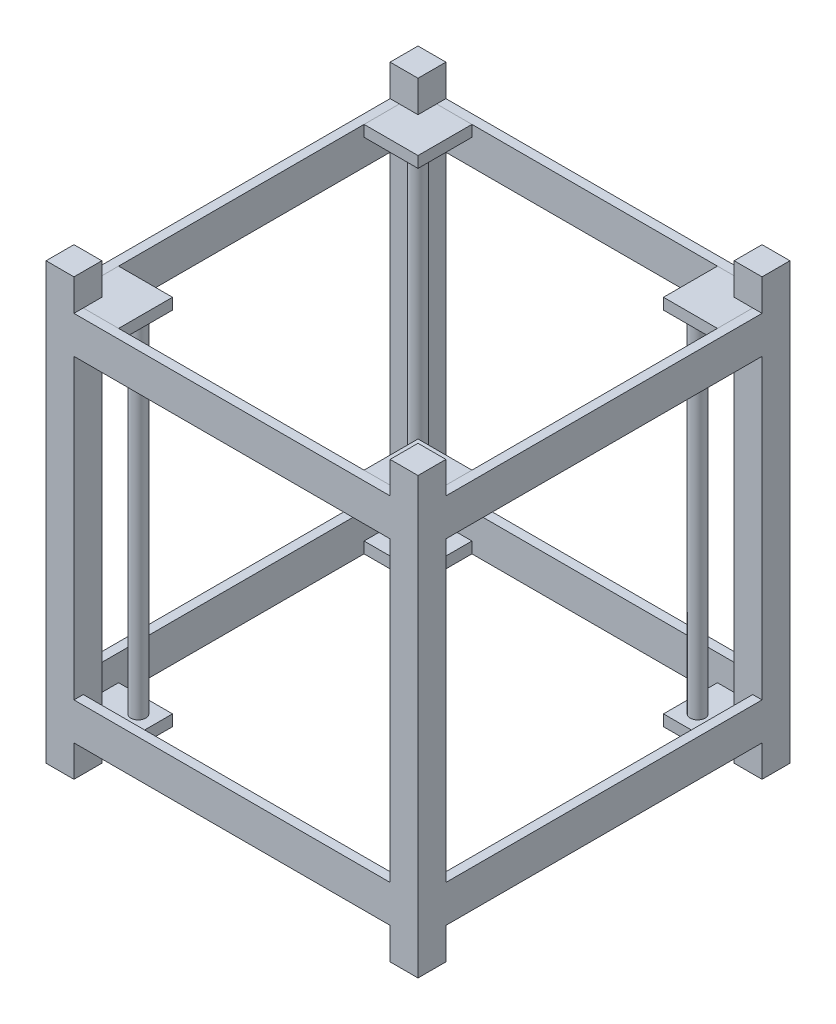
SolidWorks part; units mm, degrees
other "Frame"
ref_plane "Front Plane" through (0, 0, 0) normal (0, 0, 1) x (1, 0, 0)
ref_plane "Top Plane" through (0, 0, 0) normal (0, 1, 0) x (1, 0, 0)
ref_plane "Right Plane" through (0, 0, 0) normal (1, 0, 0) x (0, 0, -1)
sketch "Sketch2" plane through (0, 0, 0) normal (0, 1, 0) x (1, 0, 0)
  line L0 (0, 50) -> (0, -50) construction
  line L1 (-50, -50) -> (50, -50) construction
  line L2 (-50, -50) -> (-50, 50) construction
  line L3 (-50, 50) -> (50, 50) construction
  line L4 (50, -50) -> (50, 50) construction
  line L5 (-50, -50) -> (50, 50) construction
  line L6 (-50, 50) -> (50, -50) construction
  line L7 (50, 50) -> (42.5, 50)
  line L8 (50, 50) -> (50, 42.5)
  line L9 (50, 42.5) -> (42.5, 42.5) construction
  line L10 (42.5, 50) -> (42.5, 42.5) construction
  line L11 (50, 50) -> (42.5, 42.5) construction
  line L12 (50, 42.5) -> (42.5, 50) construction
  line L13 (-50, 0) -> (50, 0) construction
  line L14 (42.5, 50) -> (0, 50)
  line L15 (42.5, 47.5) -> (0, 47.5)
  line L16 (42.5, 47.5) -> (42.5, 42.5)
  line L17 (42.5, 42.5) -> (47.5, 42.5)
  line L18 (47.5, 42.5) -> (47.5, 0)
  line L19 (50, 42.5) -> (50, 0)
  line L20 (50, -42.5) -> (50, 0)
  line L21 (47.5, -42.5) -> (47.5, 0)
  line L22 (47.5, -42.5) -> (42.5, -42.5)
  line L23 (42.5, -42.5) -> (42.5, -47.5)
  line L24 (42.5, -47.5) -> (0, -47.5)
  line L25 (42.5, -50) -> (0, -50)
  line L26 (50, -50) -> (42.5, -50)
  line L27 (50, -50) -> (50, -42.5)
  line L28 (-42.5, -50) -> (0, -50)
  line L29 (-42.5, -47.5) -> (0, -47.5)
  line L30 (-42.5, -47.5) -> (-42.5, -42.5)
  line L31 (-42.5, -42.5) -> (-47.5, -42.5)
  line L32 (-47.5, -42.5) -> (-47.5, 0)
  line L33 (-50, -42.5) -> (-50, 0)
  line L34 (-50, -50) -> (-50, -42.5)
  line L35 (-50, -50) -> (-42.5, -50)
  line L36 (-50, 42.5) -> (-50, 0)
  line L37 (-47.5, 42.5) -> (-47.5, 0)
  line L38 (-47.5, 42.5) -> (-42.5, 42.5)
  line L39 (-42.5, 42.5) -> (-42.5, 47.5)
  line L40 (-42.5, 47.5) -> (0, 47.5)
  line L41 (-42.5, 50) -> (0, 50)
  line L42 (-50, 50) -> (-42.5, 50)
  line L43 (-50, 50) -> (-50, 42.5)
  point P0 (0, 0)
  point P9 (46.25, 46.25)
  dimension "D1" = 100
  dimension "D2" = 100
  dimension "D3" = 7.5
  dimension "D4" = 2.5
  dimension "D5" = 2.5
  dimension "D6" = 4
extrude "Boss-Extrude1" add sketch "Sketch2" along normal blind 10 contours L42 L43 L36 L33 L34 L35 L28 L25 L26 L27 L20 L19 L8 L7 L14 L41 L39 L40 L15 L16 L17 L18 L21 L22 L23 L24 L29 L30 L31 L32 L37 L38 region at (48.5858, 0, -46.25)
sketch "Sketch3" plane through (0, 10, 0) normal (0, 1, 0) x (1, 0, 0)
  line L0 (0, 50) -> (0, -50) construction
  line L1 (50, 50) -> (42.5, 50)
  line L2 (50, 50) -> (50, 42.5)
  line L3 (50, 42.5) -> (42.5, 42.5)
  line L4 (50, 50) -> (-50, 50)
  line L5 (-50, 50) -> (-50, -50)
  line L6 (-50, -50) -> (50, -50)
  line L7 (50, -50) -> (50, 50)
  line L8 (50, 50) -> (-50, 50) construction
  line L9 (-50, 50) -> (-50, -50) construction
  line L10 (-50, -50) -> (50, -50) construction
  line L11 (50, -50) -> (50, 50) construction
  line L12 (42.5, 50) -> (42.5, 42.5)
  line L13 (50, 50) -> (42.5, 42.5) construction
  line L14 (50, 42.5) -> (42.5, 50) construction
  line L15 (-50, 0) -> (50, 0) construction
  line L16 (50, -50) -> (50, -42.5)
  line L17 (50, -42.5) -> (42.5, -42.5)
  line L18 (42.5, -50) -> (42.5, -42.5)
  line L19 (50, -50) -> (42.5, -50)
  line L20 (-42.5, 47.5) -> (-42.5, 42.5)
  line L21 (42.5, 47.5) -> (-42.5, 47.5)
  line L22 (42.5, 42.5) -> (42.5, 47.5)
  line L23 (47.5, 42.5) -> (42.5, 42.5)
  line L24 (47.5, -42.5) -> (47.5, 42.5)
  line L25 (42.5, -42.5) -> (47.5, -42.5)
  line L26 (42.5, -47.5) -> (42.5, -42.5)
  line L27 (-42.5, -47.5) -> (42.5, -47.5)
  line L28 (-42.5, -42.5) -> (-42.5, -47.5)
  line L29 (-47.5, -42.5) -> (-42.5, -42.5)
  line L30 (-47.5, 42.5) -> (-47.5, -42.5)
  line L31 (-42.5, 42.5) -> (-47.5, 42.5)
  line L32 (-42.5, 47.5) -> (-42.5, 42.5) construction
  line L33 (42.5, 47.5) -> (-42.5, 47.5) construction
  line L34 (42.5, 42.5) -> (42.5, 47.5) construction
  line L35 (47.5, 42.5) -> (42.5, 42.5) construction
  line L36 (47.5, -42.5) -> (47.5, 42.5) construction
  line L37 (42.5, -42.5) -> (47.5, -42.5) construction
  line L38 (42.5, -47.5) -> (42.5, -42.5) construction
  line L39 (-42.5, -47.5) -> (42.5, -47.5) construction
  line L40 (-42.5, -42.5) -> (-42.5, -47.5) construction
  line L41 (-47.5, -42.5) -> (-42.5, -42.5) construction
  line L42 (-47.5, 42.5) -> (-47.5, -42.5) construction
  line L43 (-42.5, 42.5) -> (-47.5, 42.5) construction
  line L44 (-50, 50) -> (-50, 42.5)
  line L45 (-50, 42.5) -> (-42.5, 42.5)
  line L46 (-42.5, 50) -> (-42.5, 42.5)
  line L47 (-50, 50) -> (-42.5, 50)
  line L48 (-50, -50) -> (-42.5, -50)
  line L49 (-50, -50) -> (-50, -42.5)
  line L50 (-50, -42.5) -> (-42.5, -42.5)
  line L51 (-42.5, -50) -> (-42.5, -42.5)
  point P12 (46.25, 46.25)
  dimension "D1" = 0
  dimension "D2" = 0
extrude "Boss-Extrude2" add sketch "Sketch3" along normal blind 40
sketch "Sketch5" plane through (0, 0, 0) normal (0, -1, 0) x (1, 0, 0)
  line L0 (0, 50) -> (0, -50) construction
  line L1 (-50, 0) -> (50, 0) construction
  line L2 (50, -42.5) -> (50, -50)
  line L3 (42.5, 42.5) -> (50, 42.5)
  line L4 (-50, -50) -> (50, -50)
  line L5 (50, -50) -> (50, 50)
  line L6 (50, 50) -> (-50, 50)
  line L7 (-50, 50) -> (-50, -50)
  line L8 (-50, -50) -> (50, -50) construction
  line L9 (50, -50) -> (50, 50) construction
  line L10 (50, 50) -> (-50, 50) construction
  line L11 (-50, 50) -> (-50, -50) construction
  line L12 (-42.5, -42.5) -> (-42.5, -47.5)
  line L13 (-47.5, -42.5) -> (-42.5, -42.5)
  line L14 (-47.5, 42.5) -> (-47.5, -42.5)
  line L15 (-42.5, 42.5) -> (-47.5, 42.5)
  line L16 (-42.5, 47.5) -> (-42.5, 42.5)
  line L17 (42.5, 47.5) -> (-42.5, 47.5)
  line L18 (42.5, 42.5) -> (42.5, 47.5)
  line L19 (47.5, 42.5) -> (42.5, 42.5)
  line L20 (47.5, -42.5) -> (47.5, 42.5)
  line L21 (42.5, -42.5) -> (47.5, -42.5)
  line L22 (42.5, -47.5) -> (42.5, -42.5)
  line L23 (-42.5, -47.5) -> (42.5, -47.5)
  line L24 (-42.5, -42.5) -> (-42.5, -47.5) construction
  line L25 (-47.5, -42.5) -> (-42.5, -42.5) construction
  line L26 (-47.5, 42.5) -> (-47.5, -42.5) construction
  line L27 (-42.5, 42.5) -> (-47.5, 42.5) construction
  line L28 (-42.5, 47.5) -> (-42.5, 42.5) construction
  line L29 (42.5, 47.5) -> (-42.5, 47.5) construction
  line L30 (42.5, 42.5) -> (42.5, 47.5) construction
  line L31 (47.5, 42.5) -> (42.5, 42.5) construction
  line L32 (47.5, -42.5) -> (47.5, 42.5) construction
  line L33 (42.5, -42.5) -> (47.5, -42.5) construction
  line L34 (42.5, -47.5) -> (42.5, -42.5) construction
  line L35 (-42.5, -47.5) -> (42.5, -47.5) construction
  line L36 (42.5, 42.5) -> (42.5, 50)
  line L37 (42.5, 50) -> (50, 50)
  line L38 (50, 42.5) -> (50, 50)
  line L39 (42.5, 42.5) -> (50, 50) construction
  line L40 (42.5, 50) -> (50, 42.5) construction
  line L41 (42.5, -42.5) -> (50, -42.5)
  line L42 (42.5, -50) -> (50, -50)
  line L43 (42.5, -42.5) -> (42.5, -50)
  line L44 (-42.5, 42.5) -> (-50, 42.5)
  line L45 (-50, 42.5) -> (-50, 50)
  line L46 (-42.5, 50) -> (-50, 50)
  line L47 (-42.5, 42.5) -> (-42.5, 50)
  line L48 (-50, -42.5) -> (-50, -50)
  line L49 (-42.5, -50) -> (-50, -50)
  line L50 (-42.5, -42.5) -> (-42.5, -50)
  line L51 (-42.5, -42.5) -> (-50, -42.5)
  point P23 (46.25, 46.25)
  dimension "D1" = 0
  dimension "D2" = 0
extrude "Boss-Extrude8" add sketch "Sketch5" along normal blind 8.5
sketch "Sketch6" plane through (0, 0, 0) normal (0, -1, 0) x (1, 0, 0)
  line L0 (42.5, -50) -> (50, -50) construction
  line L1 (50, -50) -> (50, -42.5) construction
  line L2 (50, -42.5) -> (42.5, -42.5) construction
  line L3 (42.5, -42.5) -> (42.5, -50) construction
  line L4 (42.5, -50) -> (42.5, -47.5) construction
  line L5 (42.5, -47.5) -> (-42.5, -47.5) construction
  line L6 (-42.5, -47.5) -> (-42.5, -50) construction
  line L7 (-42.5, -50) -> (42.5, -50) construction
  line L8 (47.5, -42.5) -> (50, -42.5) construction
  line L9 (50, -42.5) -> (50, 42.5) construction
  line L10 (50, 42.5) -> (47.5, 42.5) construction
  line L11 (47.5, 42.5) -> (47.5, -42.5) construction
  line L12 (42.5, -50) -> (50, -50) construction
  line L13 (50, -50) -> (50, -42.5) construction
  line L14 (50, -42.5) -> (42.5, -42.5)
  line L15 (42.5, -42.5) -> (42.5, -50)
  line L16 (42.5, -50) -> (42.5, -47.5) construction
  line L17 (42.5, -47.5) -> (-42.5, -47.5) construction
  line L18 (-42.5, -47.5) -> (-42.5, -50)
  line L19 (-42.5, -50) -> (42.5, -50) construction
  line L20 (47.5, -42.5) -> (50, -42.5) construction
  line L21 (50, -42.5) -> (50, 42.5) construction
  line L22 (50, 42.5) -> (47.5, 42.5)
  line L23 (47.5, 42.5) -> (47.5, -42.5) construction
  line L24 (47.5, -42.5) -> (47.5, -33)
  line L25 (50, -50) -> (33, -50) construction
  line L26 (50, -50) -> (50, -33) construction
  line L27 (50, -33) -> (33, -33) construction
  line L28 (33, -50) -> (33, -33) construction
  line L29 (50, -50) -> (33, -33) construction
  line L30 (50, -33) -> (33, -50) construction
  line L31 (47.5, -33) -> (33, -33)
  line L32 (33, -33) -> (33, -47.5)
  line L33 (33, -47.5) -> (42.5, -47.5)
  point P13 (41.5, -41.5)
  line M4 (47.5, 42.5) -> (47.5, -42.5)
  dimension "D1" = 17
extrude "Boss-Extrude9" add sketch "Sketch6" against normal blind 3 separate body contours L28 L25 L15 L14 L27 M4 region at (39.609, 0, -39.609)
sketch "Sketch7" plane through (0, 3, 0) normal (0, 1, 0) x (1, 0, 0)
  line L0 (33, 33) -> (42.5, 42.5) construction
  line L6 (33, 47.5) -> (33, 33)
  line L7 (33, 33) -> (47.5, 33)
  line L8 (47.5, 33) -> (47.5, 42.5)
  line L9 (47.5, 42.5) -> (42.5, 42.5)
  line L10 (42.5, 42.5) -> (42.5, 47.5)
  line L11 (42.5, 47.5) -> (33, 47.5)
  line L12 (33, 47.5) -> (33, 33) construction
  line L13 (33, 33) -> (47.5, 33) construction
  line L14 (47.5, 33) -> (47.5, 42.5) construction
  line L15 (47.5, 42.5) -> (42.5, 42.5) construction
  line L16 (42.5, 42.5) -> (42.5, 47.5) construction
  line L17 (42.5, 47.5) -> (33, 47.5) construction
  circle A0 centre (37.6, 37.6) radius 2
  dimension "D3" = 4
  dimension "D2" = 4.6
  dimension "D1" = 0
extrude "Boss-Extrude10" add sketch "Sketch7" along normal up to surface (47 mm away) separate body contours A0 up to face at (46.25, 50, -46.25)
ref_plane "Plane1" through (0, 0, 0) normal (1, 0, 0) x (0, 0, -1)
ref_plane "Plane2" through (0, 0, 0) normal (0, 0, 1) x (1, 0, 0)
mirror "Mirror2" about plane through (0, 0, 0) normal (1, 0, 0) of bodies 114 113
mirror "Mirror3" about plane through (0, 0, 0) normal (0, 0, 1) of bodies 116 115 114 113
mirror "Mirror4" about plane through (0, 50, 0) normal (0, -1, 0) of bodies 111 118 117 116 115 114 113 120 119
combine bodies "Combine1" operation type add bodies to combine 121 111
combine bodies "Combine2" operation type add bodies to combine 118 122
combine bodies "Combine3" operation type add bodies to combine 115 125
combine bodies "Combine4" operation type add bodies to combine 114 126
combine bodies "Combine5" operation type add bodies to combine 129 119
combine bodies "Combine6" operation type add bodies to combine 113 133 127
combine bodies "Combine7" operation type add bodies to combine 116 132 124
combine bodies "Combine8" operation type add bodies to combine 117 131 123
combine bodies "Combine9" operation type add bodies to combine 128 120 134
